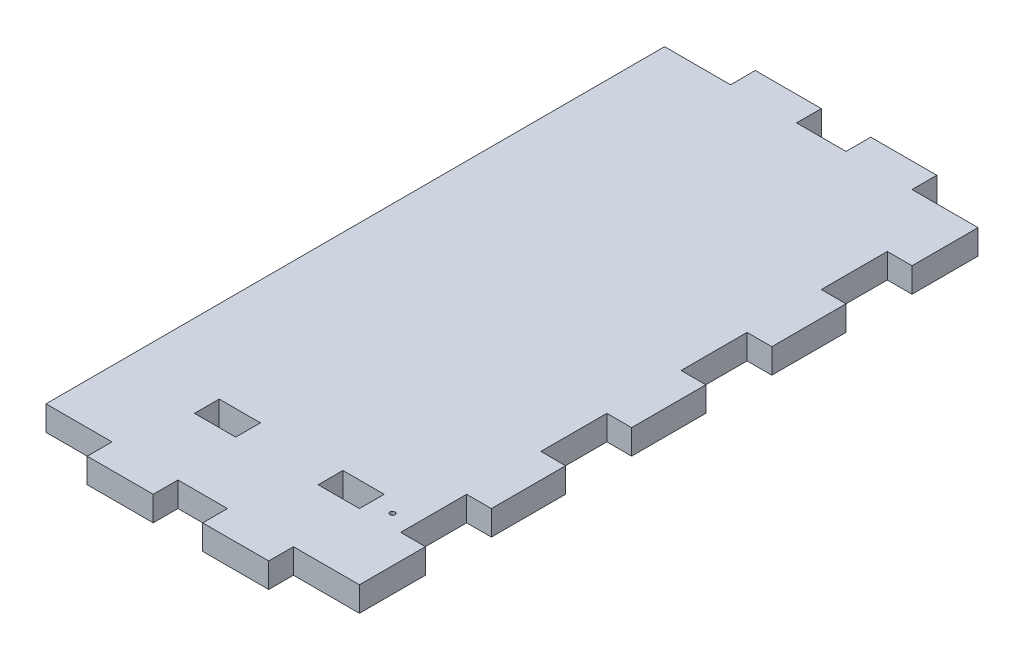
SolidWorks part; units mm, degrees
ref_plane "Front Plane" through (0, 0, 0) normal (0, 0, 1) x (1, 0, 0)
ref_plane "Top Plane" through (0, 0, 0) normal (0, 1, 0) x (1, 0, 0)
ref_plane "Right Plane" through (0, 0, 0) normal (1, 0, 0) x (0, 0, -1)
sketch "Sketch1" plane through (0, 0, 0) normal (0, 1, 0) x (1, 0, 0)
  line L0 (-25, 81) -> (-25, -81)
  line L1 (-35, 81) -> (35, 81)
  line L2 (-35, 81) -> (-35, -81)
  line L3 (-35, -81) -> (35, -81)
  line L4 (35, 81) -> (35, -81)
  line L5 (-35, 81) -> (35, -81) construction
  line L6 (-35, -81) -> (35, 81) construction
  point P0 (0, 0)
  dimension "D1" = 70
  dimension "D3" = 10
  dimension "D2" = 162
sketch "Sketch2" plane through (0, 0, 0) normal (0, 0, 1) x (1, 0, 0)
  line L0 (0, 0) -> (0, 6) construction
  line L1 (-35, 0) -> (35, 0) construction
  dimension "D1" = 6
extrude "Boss-Extrude1" add sketch "Sketch1" along normal up to vertex (6 mm away) contours L4 L1 L0 L3 | L2 L3 L0 L1 region at (5, 0, 0) region at (-30, 0, 0) up to point (0, 6, 0)
sketch "Sketch4" plane through (0, 6, 0) normal (0, 1, 0) x (1, 0, 0)
  line L0 (35, 81) -> (35, -81) construction
  line L1 (35, 81) -> (35, -81)
  line L2 (35, 81) -> (41, 81)
  line L3 (41, 81) -> (41, -81)
  line L4 (41, -81) -> (35, -81)
  dimension "D1" = 6
extrude "Boss-Extrude2" add sketch "Sketch4" against normal up to surface (6 mm away) up to face at (0, 0, 0)
sketch "Sketch5" plane through (0, 6, 0) normal (0, 1, 0) x (1, 0, 0)
  line L0 (-35, -75) -> (35, -75) construction
  line L2 (-35, 81) -> (-35, -81) construction
  line L3 (35, -75) -> (35, 0) construction
  line L5 (35, 0) -> (41, 0) construction
  line L6 (41, -81) -> (41, 81) construction
  line L7 (-35, -75) -> (-35, -81) construction
  line L8 (38, -43) -> (38, -25) construction
  line L9 (35, -59) -> (41, -59)
  line L10 (35, -59) -> (35, -43)
  line L11 (35, -43) -> (41, -43)
  line L12 (41, -59) -> (41, -43)
  line L13 (35, -9) -> (41, -9)
  line L14 (35, -9) -> (35, -25)
  line L15 (35, -25) -> (41, -25)
  line L16 (41, -9) -> (41, -25)
  line L17 (38, -9) -> (38, 9)
  line L18 (-35, -81) -> (41, -81) construction
  line L19 (41, -81) -> (25, -81)
  line L20 (41, -81) -> (41, -75)
  line L21 (41, -75) -> (25, -75)
  line L22 (25, -81) -> (25, -75)
  line L23 (-35, -75) -> (-19, -75)
  line L24 (-35, -75) -> (-35, -81)
  line L25 (-35, -81) -> (-19, -81)
  line L26 (-19, -75) -> (-19, -81)
  line L28 (-19, -81) -> (-3, -81)
  line L29 (-19, -81) -> (-19, -75)
  line L30 (-19, -75) -> (-3, -75)
  line L31 (-3, -81) -> (-3, -75)
  line L32 (25, -75) -> (9, -75)
  line L33 (25, -75) -> (25, -81)
  line L34 (25, -81) -> (9, -81)
  line L35 (9, -75) -> (9, -81)
  line L36 (-3, -75) -> (9, -75)
  line L37 (-3, -75) -> (-3, -81)
  line L38 (-3, -81) -> (9, -81)
  line L39 (9, -75) -> (9, -81)
  point P23 (38, 0)
  line M10 (-35, -81) -> (41, -81)
  line M11 (41, -81) -> (41, 81)
  line M13 (-35, 81) -> (-35, -81)
  dimension "D1" = 6
  dimension "D3" = 16
extrude "Cut-Extrude1" cut sketch "Sketch5" against normal through all contours L11 L10 L9 M11 | L14 L15 L13 M11 | L22 L21 M10 M11 | L26 L23 M13 M10 | L36 L31 L35 M10 region at (38, 6, 51) region at (38, 6, 17) region at (33, 6, 78) region at (3, 6, 78) region at (-27, 6, 78)
mirror "Mirror1" about plane through (0, 0, 0) normal (0, 0, 1) of "Cut-Extrude1"
sketch "Sketch6" plane through (0, 6, 0) normal (0, 1, 0) x (1, 0, 0)
  line L0 (25, -56) -> (35, -56) construction
  line L1 (25, -59) -> (15, -59)
  line L2 (25, -59) -> (25, -53)
  line L3 (25, -53) -> (15, -53)
  line L4 (15, -59) -> (15, -53)
  line L5 (-5, -59) -> (-15, -59)
  line L6 (-5, -59) -> (-5, -53)
  line L7 (-5, -53) -> (-15, -53)
  line L8 (-15, -59) -> (-15, -53)
  line L9 (35, -59) -> (35, -43) construction
  circle A0 centre (30, -56) radius 0.6
  dimension "D1" = 1.2
extrude "Cut-Extrude2" cut sketch "Sketch6" against normal through all
equation "\"glass_width\" = 150"
equation "\"glass_height\"= 100"
equation "\"glass_thickness\"= 4"
equation "\"brood_space\"= 42"
equation "\"t1\"= 6"
equation "\"t2\"= 3.2"
equation "\"box_depth\"= \"brood_space\" + \"glass_thickness\" + \"glass_thickness\" + \"t2\" + \"t2\""
equation "\"box_width\"= \"glass_width\" + \"t1\" + \"t1\""
equation "\"food_height\"= 70"
equation "\"box_height\" = \"glass_height\" + ( \"t1\" * 3 ) + \"food_height\""
equation "\"D1@Sketch2\"=\"t1\""
equation "\"D1@Sketch1\"=\"food_height\""
equation "\"D2@Sketch1\"=\"box_width\""
equation "\"D1@Sketch4\"=\"t1\""
equation "\"D1@Sketch5\"=\"t1\""
